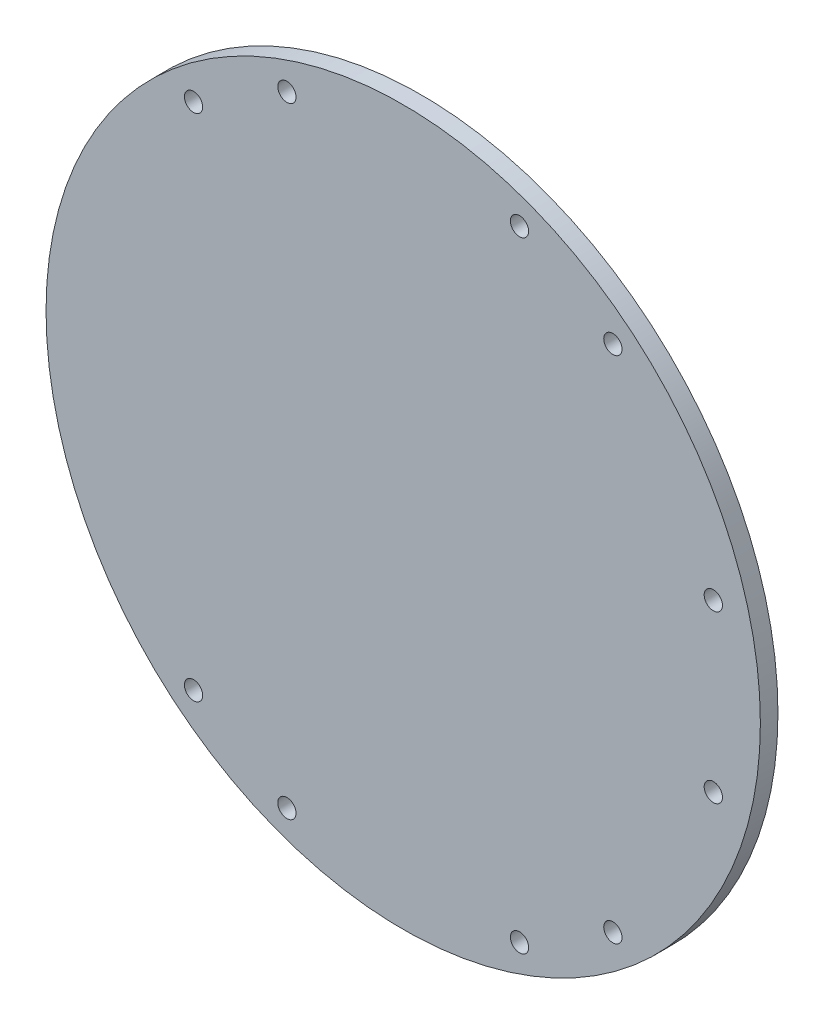
SolidWorks part; units mm, degrees
material "Acrylic (Medium-high impact)"
ref_plane "Front Plane" through (0, 0, 0) normal (0, 0, 1) x (1, 0, 0)
ref_plane "Top Plane" through (0, 0, 0) normal (0, 1, 0) x (1, 0, 0)
ref_plane "Right Plane" through (0, 0, 0) normal (1, 0, 0) x (0, 0, -1)
sketch "Sketch1" plane through (0, 0, 0) normal (0, 0, 1) x (-1, 0, 0)
  line L2 (15.1686, 58.8664) -> (15.1686, -70.1336) construction
  line L5 (79.6686, -5.6336) -> (-49.3314, -5.6336) construction
  circle A1 centre (15.1686, -5.6336) radius 64.5
  circle A15 centre (-5.8314, 50.3664) radius 1.65
  circle A16 centre (-22.6919, 40.3664) radius 1.65
  circle A17 centre (36.1686, 50.3664) radius 1.65
  circle A18 centre (53.0291, 40.3664) radius 1.65
  circle A19 centre (53.0291, -51.6336) radius 1.65
  circle A20 centre (36.1686, -61.6336) radius 1.65
  circle A21 centre (-5.8314, -61.6336) radius 1.65
  circle A22 centre (-22.6919, -51.6336) radius 1.65
  circle A23 centre (-40.8314, 9.3664) radius 1.65
  circle A24 centre (-40.8314, -20.6336) radius 1.65
  dimension "D3" = 3.3
  dimension "D4" = 15
  dimension "D10" = 3.3
  dimension "D11" = 56
  dimension "D12" = 46
  dimension "D20" = 129
  dimension "D5" = 56
  dimension "D14" = 21
extrude "Boss-Extrude1" add sketch "Sketch1" along normal blind 3.175
